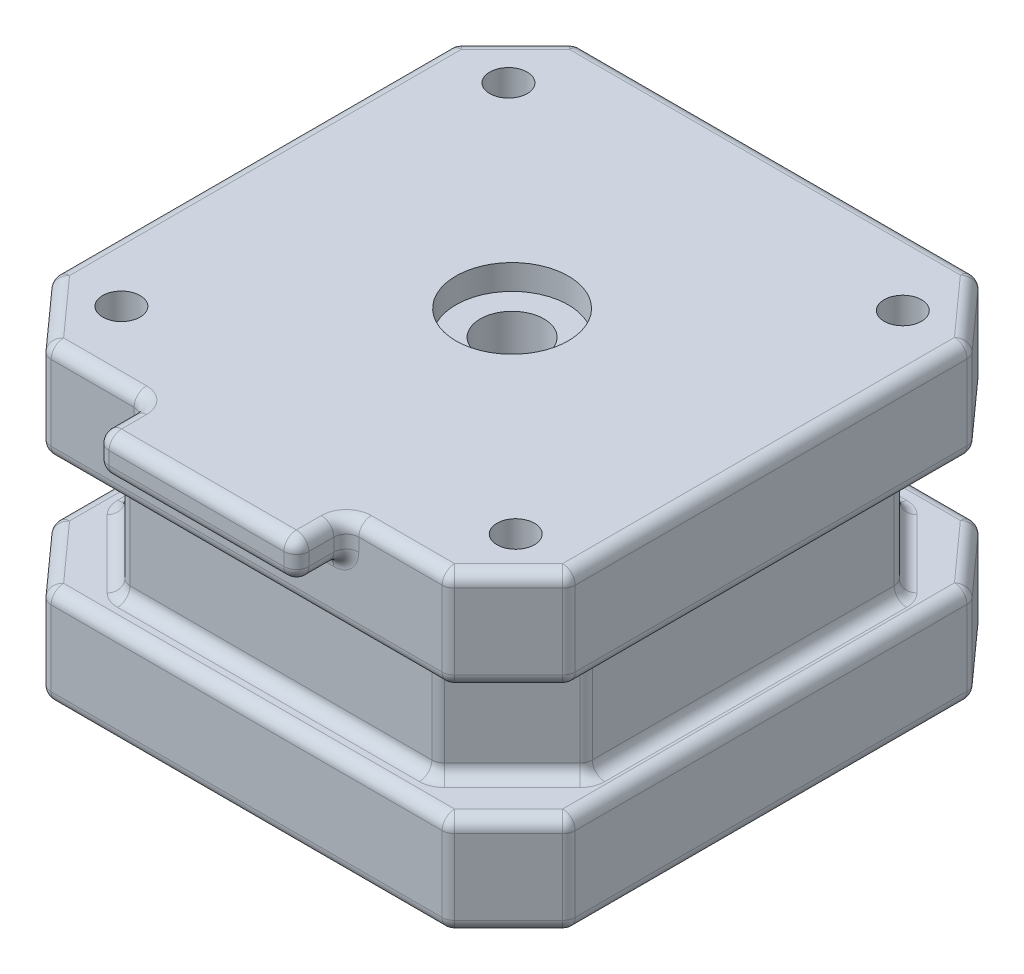
SolidWorks part; units mm, degrees
ref_plane "Front Plane" through (0, 0, 0) normal (0, 0, 1) x (1, 0, 0)
ref_plane "Top Plane" through (0, 0, 0) normal (0, 1, 0) x (1, 0, 0)
ref_plane "Right Plane" through (0, 0, 0) normal (1, 0, 0) x (0, 0, -1)
sketch "Sketch1" plane through (0, 0, 0) normal (0, 1, 0) x (1, 0, 0)
  line L0 (16.085, 21.2606) -> (-16.085, 21.2606)
  line L1 (-16.085, 21.2606) -> (-20.9994, 16.3462)
  line L2 (-20.9994, 16.3462) -> (-20.9994, -15.8238)
  line L3 (-20.9994, -15.8238) -> (-16.3609, -20.9994)
  line L4 (-16.3609, -20.9994) -> (15.8091, -20.9994)
  line L5 (15.8091, -20.9994) -> (20.7235, -16.085)
  line L6 (20.7235, -16.085) -> (20.7235, 16.085)
  line L7 (20.7235, 16.085) -> (16.085, 21.2606)
  point P2 (0, 21.2606)
  point P9 (20.7235, 0)
  dimension "D1" = 6.95
  dimension "D2" = 6.95
  dimension "D3" = 32.17
  dimension "D4" = 32.17
extrude "Boss-Extrude1" add sketch "Sketch1" along normal blind 8.02
sketch "Sketch2" plane through (0, 0, 0) normal (0, -1, 0) x (1, 0, 0)
  line L0 (-15.79, 15.5) -> (15.79, 15.5) construction
  line L1 (15.79, 15.5) -> (15.79, -15.5) construction
  circle A0 centre (-15.79, 15.5) radius 1.5
  circle A1 centre (15.79, 15.5) radius 1.5
  circle A2 centre (-15.79, -15.5) radius 1.5
  circle A3 centre (15.79, -15.5) radius 1.5
  point P8 (0, 15.5)
  point P9 (15.79, 0)
  dimension "D1" = 3
  dimension "D2" = 31.58
  dimension "D3" = 31
extrude "Cut-Extrude1" cut sketch "Sketch2" against normal blind 6
sketch "Sketch3" plane through (0, 0, 0) normal (0, -1, 0) x (1, 0, 0)
  circle A0 centre (0, 0) radius 11
  circle A1 centre (0, 0) radius 4.5
  dimension "D1" = 22
  dimension "D2" = 9
extrude "Boss-Extrude2" add sketch "Sketch3" along normal blind 2
sketch "Sketch5" plane through (0, 8.02, 0) normal (0, 1, 0) x (1, 0, 0)
  line L0 (-18.5104, 12.5) -> (-12.5, 18.5104)
  line L1 (-12.5, 18.5104) -> (12.5, 18.5104)
  line L2 (12.5, 18.5104) -> (18.5104, 12.5)
  line L3 (18.5104, 12.5) -> (18.5104, -12.5)
  line L4 (18.5104, -12.5) -> (12.5, -18.5104)
  line L5 (12.5, -18.5104) -> (-12.5, -18.5104)
  line L6 (-12.5, -18.5104) -> (-18.5104, -12.5)
  line L7 (-18.5104, -12.5) -> (-18.5104, 12.5)
  point P6 (0, 18.5104)
  point P9 (-18.5104, 0)
  dimension "D1" = 25
  dimension "D2" = 25
  dimension "D3" = 8.5
  dimension "D4" = 8.5
extrude "Boss-Extrude3" add sketch "Sketch5" along normal blind 9
ref_plane "Plane1" through (0, 12.52, 0) normal (0, -1, 0) x (-1, 0, 0)
mirror "Mirror1" about plane through (0, 12.52, 0) normal (0, -1, 0) of "Boss-Extrude1", "Cut-Extrude1"
sketch "Sketch4" plane through (0, 0, 0) normal (0, -1, 0) x (1, 0, 0)
  circle A0 centre (0, 0) radius 2.55
  dimension "D1" = 5.1
extrude "Cut-Extrude2" cut sketch "Sketch4" against normal through all
sketch "Sketch6" plane through (0, 25.04, 0) normal (0, 1, 0) x (1, 0, 0)
  circle A0 centre (0, 0) radius 4.5
  dimension "D1" = 9
extrude "Cut-Extrude3" cut sketch "Sketch6" against normal blind 2
sketch "Sketch8" plane through (0, 25.04, 0) normal (0, 1, 0) x (1, 0, 0)
  line L0 (-16.3609, -20.9994) -> (15.8091, -20.9994) construction
  line L1 (-8.2759, -20.9994) -> (7.7241, -20.9994)
  line L2 (-8.2759, -20.9994) -> (-8.2759, -24.9994)
  line L3 (-8.2759, -24.9994) -> (7.7241, -24.9994)
  line L4 (7.7241, -20.9994) -> (7.7241, -24.9994)
  line L5 (-16.3609, -20.9994) -> (15.8091, -20.9994)
  point P6 (-0.2759, -20.9994)
  point P7 (-0.2759, -20.9994)
  line M16 (-16.3609, -20.9994) -> (15.8091, -20.9994)
  dimension "D1" = 4
  dimension "D2" = 16
extrude "Boss-Extrude5" add sketch "Sketch8" against normal blind 3.04 contours L4 L2 L3 M16 region at (-0.2759, 25.04, 22.9994)
fillet "Fillet1" radius 1 84 edges at (7.7241, 23.52, 20.9994) (7.7241, 23.52, 24.9994) (-8.2759, 23.52, 24.9994) (-8.2759, 23.52, 20.9994) (-0.2759, 22, 20.9994) (-8.2759, 22, 22.9994) (-0.2759, 22, 24.9994) (7.7241, 22, 22.9994) (12.5, 12.52, -18.5104) (-12.5, 12.52, -18.5104) (-18.5104, 12.52, -12.5) (18.5104, 12.52, -12.5) (-18.5104, 12.52, 12.5) (18.5104, 12.52, 12.5) (-12.5, 12.52, 18.5104) (12.5, 12.52, 18.5104) (-16.085, 4.01, -21.2606) (-20.9994, 4.01, -16.3462) (-20.9994, 21.03, -16.3462) (-16.085, 21.03, -21.2606) (-16.3609, 21.03, 20.9994) (-20.9994, 21.03, 15.8238) (20.7235, 21.03, 16.085) (15.8091, 21.03, 20.9994) (16.085, 21.03, -21.2606) (20.7235, 21.03, -16.085) (20.7235, 4.01, -16.085) (16.085, 4.01, -21.2606) (20.7235, 4.01, 16.085) (-16.3609, 4.01, 20.9994) (15.8091, 4.01, 20.9994) (20.7235, 8.02, 0) (18.2663, 8.02, 18.5422) (-0.2759, 8.02, 20.9994) (-18.6801, 8.02, 18.4116) (-20.9994, 8.02, -0.2612) (-18.5422, 8.02, -18.8034) (0, 8.02, -21.2606) (18.4043, 8.02, -18.6728) (-15.5052, 8.02, 15.5052) (0, 8.02, 18.5104) (15.5052, 8.02, 15.5052) (18.5104, 8.02, 0) (15.5052, 8.02, -15.5052) (0, 8.02, -18.5104) (-15.5052, 8.02, -15.5052) (-18.5104, 8.02, 0) (0, 0, -21.2606) (-18.5422, 0, -18.8034) (-20.9994, 0, -0.2612) (-18.6801, 0, 18.4116) (-0.2759, 0, 20.9994) (18.2663, 0, 18.5422) (20.7235, 0, 0) (18.4043, 0, -18.6728) (0, 17.02, -21.2606) (-18.5422, 17.02, -18.8034) (-20.9994, 17.02, -0.2612) (-18.6801, 17.02, 18.4116) (-0.2759, 17.02, 20.9994) (18.2663, 17.02, 18.5422) (20.7235, 17.02, 0) (18.4043, 17.02, -18.6728) (0, 17.02, -18.5104) (15.5052, 17.02, -15.5052) (18.5104, 17.02, 0) (15.5052, 17.02, 15.5052) (0, 17.02, 18.5104) (-15.5052, 17.02, 15.5052) (-18.5104, 17.02, 0) (-15.5052, 17.02, -15.5052) (20.7235, 25.04, 0) (18.2663, 25.04, 18.5422) (11.7666, 25.04, 20.9994) (7.7241, 25.04, 22.9994) (-0.2759, 25.04, 24.9994) (-8.2759, 25.04, 22.9994) (-12.3184, 25.04, 20.9994) (-18.6801, 25.04, 18.4116) (-20.9994, 25.04, -0.2612) (-18.5422, 25.04, -18.8034) (0, 25.04, -21.2606) (18.4043, 25.04, -18.6728) (-20.9994, 4.01, 15.8238)
